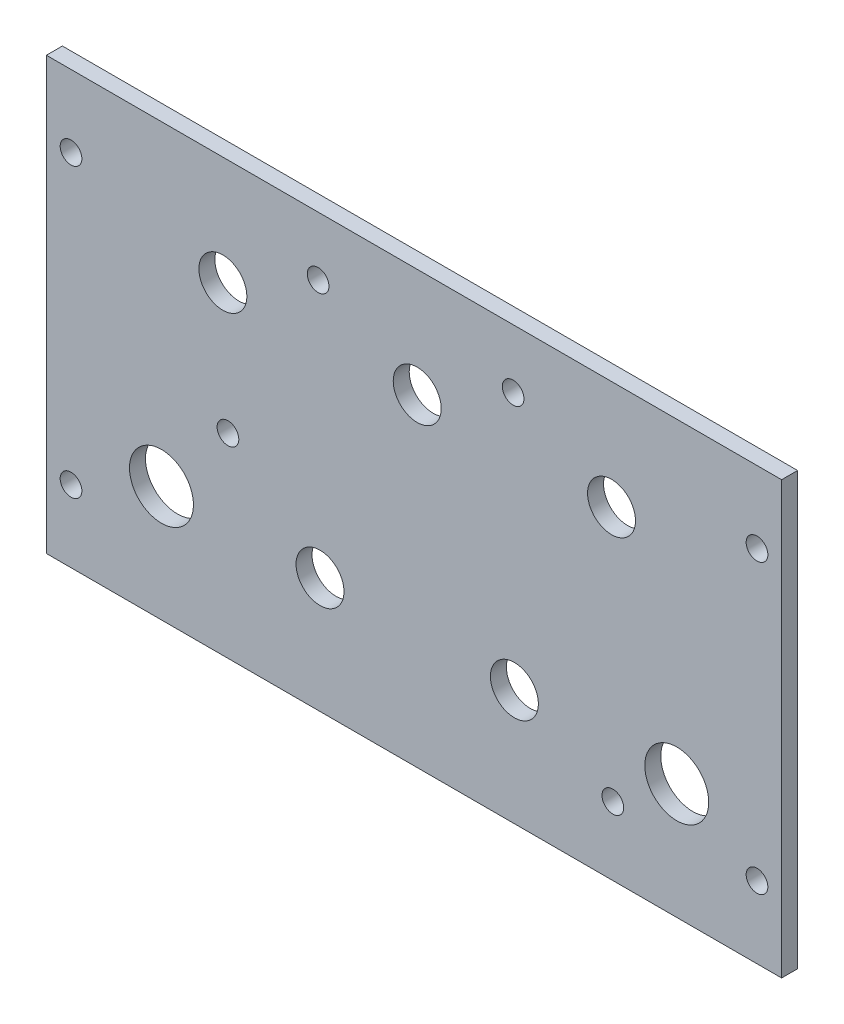
SolidWorks part; units mm, degrees
ref_plane "Front Plane" through (0, 0, 0) normal (0, 0, 1) x (1, 0, 0)
ref_plane "Top Plane" through (0, 0, 0) normal (0, 1, 0) x (1, 0, 0)
ref_plane "Right Plane" through (0, 0, 0) normal (1, 0, 0) x (0, 0, -1)
sketch "Sketch1" plane through (0, 0, 0) normal (0, 0, 1) x (1, 0, 0)
  line L4 (0, 85.725) -> (-146.05, 85.725)
  line L5 (-146.05, 85.725) -> (-146.05, 0)
  line L6 (-146.05, 0) -> (0, 0)
  line L7 (0, 0) -> (0, 85.725)
  line L8 (0, 85.725) -> (-146.05, 85.725)
  line L9 (-146.05, 85.725) -> (-146.05, 0)
  line L10 (-146.05, 0) -> (0, 0)
  line L11 (0, 0) -> (0, 85.725)
  dimension "D1" = 0
extrude "Boss-Extrude1" add sketch "Sketch1" against normal blind 3.175
hole_wizard "#6 Clearance Hole1" positions "Sketch3" profile "Sketch2" hole size "#6" standard "ANSI Inch"
sketch "Sketch3" plane through (0, 0, -3.175) normal (0, 0, -1) x (-1, 0, 0)
  point P0 (4.8895, 71.4375)
  point P3 (53.34, 74.041)
  point P6 (92.075, 74.041)
  point P9 (141.1605, 71.4375)
  point P12 (109.982, 38.735)
  point P15 (141.1605, 14.2875)
  point P18 (33.528, 13.589)
  point P21 (4.8895, 14.2875)
sketch "Sketch2" plane through (-4.8895, 71.4375, -3.175) normal (1, 0, 0) x (0, 1, 0)
  line L0 (0, 0) -> (0, 13.9934)
  line L1 (0, 13.9934) -> (2.1526, 12.7)
  line L2 (2.1526, 12.7) -> (2.1526, 0)
  line L5 (2.1526, 0) -> (0, 0)
  line L10 (0, 13.9934) -> (-2.1526, 12.7) construction
  line L11 (0, -6.35) -> (0, 107.95) construction
  dimension "Hole Dia." = 4.3053
  dimension "Hole Depth" = 12.7
  dimension "Drill Angle" = 118
sketch "Sketch4" plane through (0, 0, -3.175) normal (0, 0, -1) x (-1, 0, 0)
  circle A0 centre (20.828, 22.987) radius 6.35
  circle A1 centre (123.19, 22.987) radius 6.35
  circle A2 centre (33.782, 64.135) radius 4.7625
  circle A3 centre (72.39, 64.135) radius 4.7625
  circle A4 centre (110.998, 64.135) radius 4.7625
  circle A5 centre (91.694, 22.987) radius 4.7625
  circle A6 centre (53.086, 22.987) radius 4.7625
  dimension "D1" = 12.7
  dimension "D2" = 9.525
extrude "Cut-Extrude1" cut sketch "Sketch4" against normal through all
